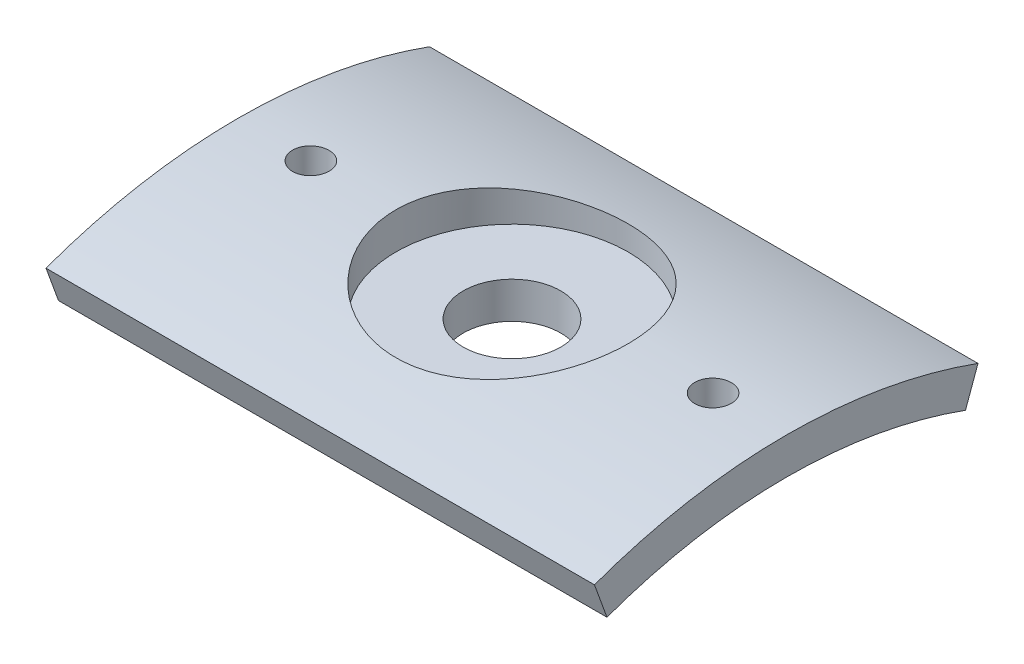
SolidWorks part; units mm, degrees
ref_plane "Front Plane" through (0, 0, 0) normal (0, 0, 1) x (1, 0, 0)
ref_plane "Top Plane" through (0, 0, 0) normal (0, 1, 0) x (1, 0, 0)
ref_plane "Right Plane" through (0, 0, 0) normal (1, 0, 0) x (0, 0, -1)
sketch "Sketch1" plane through (0, 0, 0) normal (1, 0, 0) x (0, 0, -1)
  line L0 (0, 0) -> (0, -46) construction
  line L1 (-14.7069, -5.5932) -> (-15.7329, -2.7741)
  line L2 (14.7069, -5.5932) -> (15.7329, -2.7741)
  arc A0 (-15.7329, -2.7741) -> (15.7329, -2.7741) centre (0, -46) cw
  arc A1 (-14.7069, -5.5932) -> (14.7069, -5.5932) centre (0, -46) cw
  dimension "D2" = 46
  dimension "D1" = 3
extrude "Boss-Extrude1" add sketch "Sketch1" along normal blind 45
ref_plane "Plane1" through (0, -3, 0) normal (0, 1, 0) x (1, 0, 0)
sketch "Sketch2" plane through (0, -3, 0) normal (0, 1, 0) x (1, 0, 0)
  line L0 (0, 0) -> (22.5, 0) construction
  circle A0 centre (22.5, 0) radius 12.5
  dimension "D1" = 25
extrude "Boss-Extrude2" add sketch "Sketch2" against normal blind 3
sketch "Sketch3" plane through (0, -3, 0) normal (0, 1, 0) x (1, 0, 0)
  line L0 (0, 0) -> (22.5, 0) construction
  circle A0 centre (22.5, 0) radius 9.525
  dimension "D2" = 19.05
  dimension "D1" = 22.5
extrude "Cut-Extrude1" cut sketch "Sketch3" along normal blind 14
sketch "Sketch4" plane through (0, -3, 0) normal (0, 1, 0) x (1, 0, 0)
  circle A0 centre (22.5, 0) radius 4
  dimension "D1" = 8
extrude "Cut-Extrude2" cut sketch "Sketch4" against normal blind 14
sketch "Sketch5" plane through (0, -3, 0) normal (0, 1, 0) x (1, 0, 0)
  line L0 (0, 0) -> (6, 0) construction
  line L1 (6, 0) -> (22.5, 0) construction
  line L2 (22.5, 0) -> (22.5, 14.84) construction
  circle A0 centre (6, 0) radius 1.5
  circle A1 centre (39, 0) radius 1.5
  dimension "D2" = 3
  dimension "D1" = 6
extrude "Cut-Extrude3" cut sketch "Sketch5" against normal blind 14 and the other way blind 14
